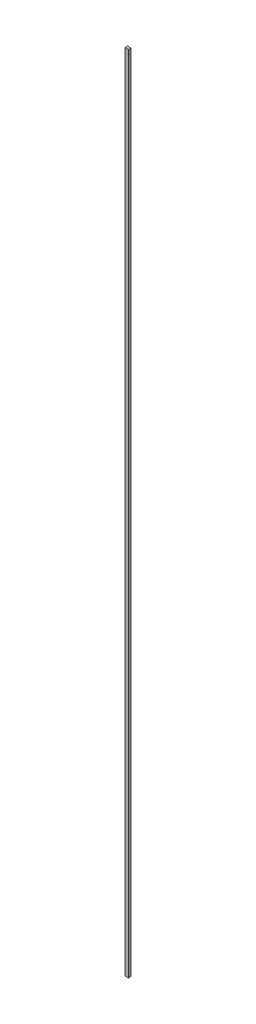
SolidWorks part; units mm, degrees
ref_plane "Front Plane" through (0, 0, 0) normal (0, 0, 1) x (1, 0, 0)
ref_plane "Top Plane" through (0, 0, 0) normal (0, 1, 0) x (1, 0, 0)
ref_plane "Right Plane" through (0, 0, 0) normal (1, 0, 0) x (0, 0, -1)
sketch "Sketch1" plane through (0, 0, 0) normal (0, 1, 0) x (1, 0, 0)
  line L1 (-3.175, -2.3812) -> (3.175, -2.3812)
  line L2 (-3.175, -2.3812) -> (-3.175, 2.3813)
  line L3 (-3.175, 2.3813) -> (3.175, 2.3813)
  line L4 (3.175, -2.3812) -> (3.175, 2.3813)
  line L5 (-3.175, -2.3812) -> (3.175, 2.3813) construction
  line L6 (-3.175, 2.3813) -> (3.175, -2.3812) construction
  point P0 (0, 0)
  dimension "D1" = 6.35
  dimension "D2" = 4.7625
extrude "Boss-Extrude1" add sketch "Sketch1" along normal blind 736.6 and the other way blind 736.6
